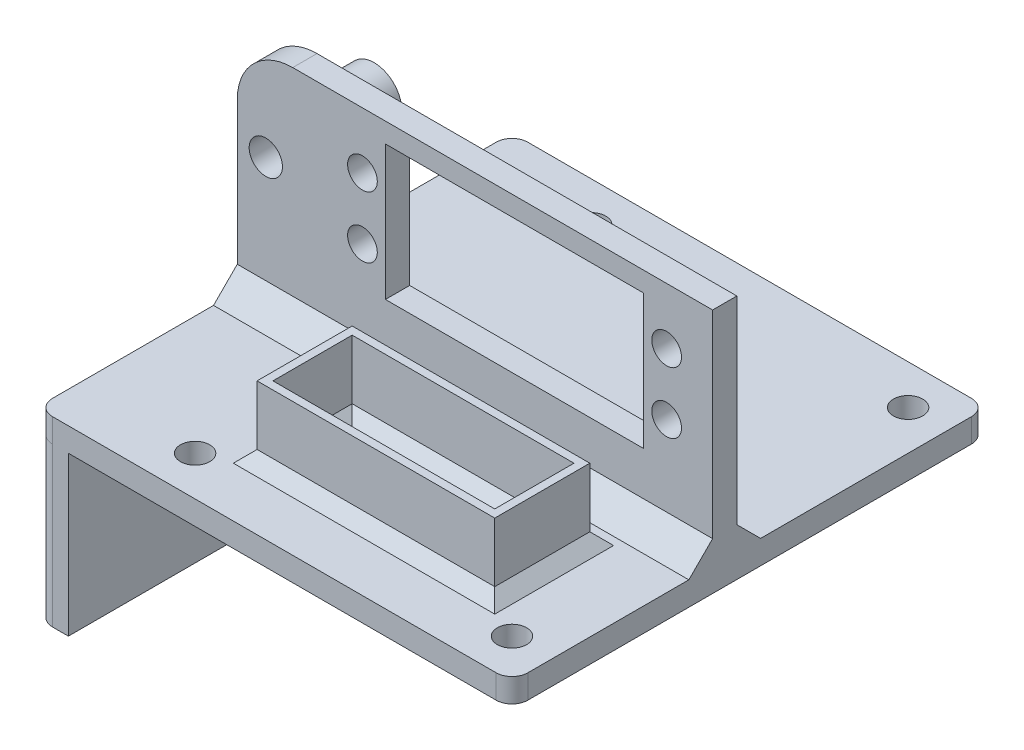
SolidWorks part; units mm, degrees
material "PET"
ref_plane "Front Plane" through (0, 0, 0) normal (0, 0, 1) x (1, 0, 0)
ref_plane "Top Plane" through (0, 0, 0) normal (0, 1, 0) x (1, 0, 0)
ref_plane "Right Plane" through (0, 0, 0) normal (1, 0, 0) x (0, 0, -1)
sketch "Sketch1" plane through (0, 0, 0) normal (0, 0, 1) x (1, 0, 0)
  line L1 (-38.1, -17.78) -> (38.1, -17.78)
  line L2 (-38.1, -17.78) -> (-38.1, 17.78)
  line L3 (-38.1, 17.78) -> (38.1, 17.78)
  line L4 (38.1, -17.78) -> (38.1, 17.78)
  line L5 (-38.1, -17.78) -> (38.1, 17.78) construction
  line L6 (-38.1, 17.78) -> (38.1, -17.78) construction
  point P0 (0, 0)
  dimension "D1" = 76.2
  dimension "D2" = 35.56
extrude "Boss-Extrude1" add sketch "Sketch1" along normal mid plane 3.81
sketch "Sketch2" plane through (0, 0, 1.905) normal (0, 0, 1) x (1, 0, 0)
  line L0 (0, 17.78) -> (0, 0) construction
  line L1 (38.1, 17.78) -> (-38.1, 17.78) construction
  line L2 (6.35, 3.81) -> (30.734, 3.81) construction
  line L5 (-18.034, -1.1149) -> (30.734, -1.1149) construction
  line L6 (-18.034, -1.1149) -> (-18.034, 8.7349) construction
  line L7 (-18.034, 8.7349) -> (30.734, 8.7349) construction
  line L8 (30.734, -1.1149) -> (30.734, 8.7349) construction
  line L9 (-18.034, -1.1149) -> (30.734, 8.7349) construction
  line L10 (-18.034, 8.7349) -> (30.734, -1.1149) construction
  line L11 (6.35, 3.81) -> (6.35, 8.7349) construction
  circle A0 centre (-18.034, 8.7349) radius 2.3813
  circle A1 centre (30.734, 8.7349) radius 2.3812
  circle A2 centre (30.734, -1.1149) radius 2.3812
  circle A3 centre (-18.034, -1.1149) radius 2.3813
  point P9 (6.35, 3.81)
  dimension "D4" = 4.7625
  dimension "D1" = 3.81
  dimension "D2" = 48.768
  dimension "D3" = 9.8499
  dimension "D5" = 6.35
extrude "Cut-Extrude1" cut sketch "Sketch2" against normal blind 6.35
sketch "Sketch3" plane through (0, 0, 1.905) normal (0, 0, 1) x (1, 0, 0)
  line L1 (-18.034, 8.7349) -> (-18.034, -1.1149) construction
  line L2 (-14.351, -6.985) -> (27.051, -6.985)
  line L3 (-14.351, -6.985) -> (-14.351, 14.605)
  line L4 (-14.351, 14.605) -> (27.051, 14.605)
  line L5 (27.051, -6.985) -> (27.051, 14.605)
  line L6 (-14.351, -6.985) -> (27.051, 14.605) construction
  line L7 (-14.351, 14.605) -> (27.051, -6.985) construction
  line L8 (-18.034, 3.81) -> (38.1, 3.81) construction
  line L10 (38.1, -17.78) -> (38.1, 17.78) construction
  point P0 (6.35, 3.81)
  point P6 (6.35, 3.81)
  dimension "D1" = 21.59
  dimension "D2" = 6.35
  dimension "D3" = 41.402
extrude "Cut-Extrude2" cut sketch "Sketch3" against normal up to surface (3.81 mm away) up to face at (-20.4153, -1.1149, -1.905)
sketch "Sketch5" plane through (0, -17.78, 0) normal (0, -1, 0) x (1, 0, 0)
  line L0 (-38.1, 1.905) -> (-38.1, -1.905) construction
  line L1 (-38.1, -26.67) -> (38.1, -26.67)
  line L2 (-38.1, -26.67) -> (-38.1, 49.53)
  line L3 (-38.1, 49.53) -> (38.1, 49.53)
  line L4 (38.1, -26.67) -> (38.1, 49.53)
  line L5 (-38.1, -26.67) -> (38.1, 49.53) construction
  line L6 (-38.1, 49.53) -> (38.1, -26.67) construction
  point P0 (0, 11.43)
  dimension "D1" = 76.2
  dimension "D2" = 76.2
  dimension "D3" = 11.43
extrude "Boss-Extrude2" add sketch "Sketch5" along normal blind 3.81
sketch "Sketch8" plane through (0, 0, -1.905) normal (0, 0, -1) x (-1, 0, 0)
  line L0 (-38.1, 17.78) -> (38.1, 17.78) construction
  line L1 (38.1, 17.78) -> (38.1, -17.78) construction
  circle A0 centre (33.528, 3.175) radius 2.667
  dimension "D1" = 5.334
  dimension "D2" = 14.605
  dimension "D3" = 4.572
extrude "Cut-Extrude5" cut sketch "Sketch8" against normal up to surface (3.81 mm away) up to face at (6.35, 3.81, 1.905)
sketch "Sketch9" plane through (0, 0, -1.905) normal (0, 0, -1) x (-1, 0, 0)
  circle A0 centre (33.528, 3.175) radius 2.667
  circle A1 centre (33.528, 3.175) radius 4.445
  circle A2 centre (33.528, 3.175) radius 2.667 construction
  circle M3 centre (33.528, 3.175) radius 2.667
  dimension "D1" = 8.89
extrude "Boss-Extrude4" add sketch "Sketch9" along normal blind 6.096 contours A1 M3 | A0
sketch "Sketch10" plane through (0, 0, -1.905) normal (0, 0, -1) x (-1, 0, 0)
  line L0 (38.1, -17.78) -> (-38.1, -17.78) construction
  line L1 (30.0355, 0.4254) -> (37.0205, 0.4254)
  line L2 (30.0355, 0.4254) -> (30.0355, -17.78)
  line L3 (30.0355, -17.78) -> (37.0205, -17.78)
  line L4 (37.0205, 0.4254) -> (37.0205, -17.78)
  line L5 (33.528, 5.842) -> (33.528, -21.59) construction
  line L6 (38.1, -21.59) -> (-38.1, -21.59) construction
  circle A0 centre (33.528, 3.175) radius 4.445 construction
  circle A1 centre (33.528, 3.175) radius 2.667 construction
  point P15 (33.528, 0.4254)
  dimension "D1" = 6.985
extrude "Boss-Extrude5" add sketch "Sketch10" along normal up to surface (6.096 mm away) up to face at (-36.195, 3.175, -8.001)
sketch "Sketch11" plane through (0, 0, 1.905) normal (0, 0, 1) x (1, 0, 0)
  circle A0 centre (-33.528, 3.175) radius 2.667
  circle A1 centre (-33.528, 3.175) radius 4.445
  circle A2 centre (-33.528, 3.175) radius 2.667 construction
  dimension "D1" = 8.89
extrude "Boss-Extrude6" add sketch "Sketch11" along normal blind 5.08
sketch "Sketch12" plane through (0, 0, 1.905) normal (0, 0, 1) x (1, 0, 0)
  line L0 (-33.528, 5.842) -> (-33.528, -17.78) construction
  line L1 (38.1, -17.78) -> (-38.1, -17.78) construction
  line L2 (-38.1, -17.78) -> (38.1, -17.78) construction
  line L3 (-37.0205, 0.4254) -> (-30.0355, 0.4254)
  line L4 (-37.0205, 0.4254) -> (-37.0205, -17.78)
  line L5 (-37.0205, -17.78) -> (-30.0355, -17.78)
  line L6 (-30.0355, 0.4254) -> (-30.0355, -17.78)
  circle A0 centre (-33.528, 3.175) radius 2.667 construction
  circle A1 centre (-33.528, 3.175) radius 4.445 construction
  point P6 (-33.528, 3.175)
  point P16 (-33.528, -17.78)
  dimension "D1" = 6.985
extrude "Boss-Extrude7" add sketch "Sketch12" along normal up to surface (5.08 mm away) up to face at (-29.083, 3.175, 6.985)
sketch "Sketch13" plane through (0, -17.78, 0) normal (0, 1, 0) x (1, 0, 0)
  line L0 (0, -49.53) -> (0, 26.67) construction
  line L1 (38.1, -49.53) -> (-38.1, -49.53) construction
  line L2 (-38.1, 26.67) -> (38.1, 26.67) construction
  line L3 (-38.1, 0) -> (38.1, 0) construction
  line L4 (-38.1, -1.905) -> (-38.1, 1.905) construction
  line L5 (38.1, -1.905) -> (38.1, 1.905) construction
  line L8 (-38.1, 1.905) -> (-38.1, 26.67) construction
  line L9 (38.1, 26.67) -> (38.1, 1.905) construction
  line L10 (-38.1, 26.67) -> (-38.1, -49.53) construction
  line L11 (-38.1, -49.53) -> (-38.1, -1.905) construction
  line L12 (-38.1, -11.43) -> (38.1, -11.43) construction
  line L13 (38.1, -1.905) -> (38.1, -49.53) construction
  circle A4 centre (-19.05, 20.32) radius 2.3495
  circle A6 centre (31.75, 20.32) radius 2.3495
  circle A7 centre (31.75, -43.18) radius 2.3495
  circle A8 centre (-19.05, -43.18) radius 2.3495
  dimension "D6" = 4.699
  dimension "D7" = 19.05
  dimension "D8" = 6.35
  dimension "D9" = 6.35
  dimension "D10" = 6.35
extrude "Cut-Extrude6" cut sketch "Sketch13" against normal through all
sketch "Sketch14" plane through (0, 0, 1.905) normal (0, 0, 1) x (1, 0, 0)
  line L0 (-14.351, -6.985) -> (27.051, -6.985) construction
  line L1 (27.051, -6.985) -> (27.051, 14.605) construction
  line L2 (-14.351, 14.605) -> (-14.351, -6.985) construction
  line L3 (27.051, 14.605) -> (-14.351, 14.605) construction
  line L4 (-14.351, -6.985) -> (27.051, -6.985)
  line L5 (27.051, -6.985) -> (27.051, 14.605)
  line L6 (-14.351, 14.605) -> (-14.351, -6.985)
  line L7 (-37.0205, -17.78) -> (-37.0205, 0.4254)
  line L8 (-30.0355, 0.4254) -> (-30.0355, -17.78)
  line L9 (-30.0355, -17.78) -> (38.1, -17.78)
  line L10 (38.1, -17.78) -> (38.1, 17.78)
  line L11 (38.1, 17.78) -> (-38.1, 17.78)
  line L12 (-38.1, 17.78) -> (-38.1, -17.78)
  line L13 (-38.1, -17.78) -> (-37.0205, -17.78)
  line L16 (-30.0355, -17.78) -> (38.1, -17.78)
  line L17 (38.1, -17.78) -> (38.1, 17.78)
  line L18 (38.1, 17.78) -> (-38.1, 17.78)
  line L19 (-38.1, 17.78) -> (-38.1, -17.78)
  line L20 (-38.1, -17.78) -> (-37.0205, -17.78)
  line L21 (27.051, 14.605) -> (-14.351, 14.605)
  line L22 (-37.0205, -17.78) -> (-30.0355, -17.78)
  circle A0 centre (30.734, -1.1149) radius 2.3812 construction
  arc A1 (-30.0355, 0.4254) -> (-37.0205, 0.4254) centre (-33.528, 3.175) ccw
  circle A3 centre (30.734, 8.7349) radius 2.3812 construction
  circle A4 centre (-18.034, -1.1149) radius 2.3813 construction
  circle A5 centre (-18.034, 8.7349) radius 2.3813 construction
  circle A6 centre (30.734, -1.1149) radius 2.3812
  circle A7 centre (30.734, 8.7349) radius 2.3812
  circle A8 centre (-18.034, -1.1149) radius 2.3813
  circle A9 centre (-18.034, 8.7349) radius 2.3813
  circle A10 centre (-33.528, 3.175) radius 2.667 construction
  circle A11 centre (-33.528, 3.175) radius 2.667
  dimension "D1" = 0
extrude "Boss-Extrude8" add sketch "Sketch14" along normal blind 15.466
sketch "Sketch15" plane through (0, 0, -1.905) normal (0, 0, -1) x (-1, 0, 0)
  line L0 (14.351, -6.985) -> (-27.051, -6.985) construction
  line L1 (14.351, 14.605) -> (14.351, -6.985) construction
  line L2 (-27.051, -6.985) -> (-27.051, 14.605) construction
  line L3 (-27.051, 14.605) -> (14.351, 14.605) construction
  line L4 (14.351, -6.985) -> (-27.051, -6.985)
  line L5 (14.351, 14.605) -> (14.351, -6.985)
  line L6 (-27.051, -6.985) -> (-27.051, 14.605)
  line L7 (-38.1, -17.78) -> (30.0355, -17.78)
  line L8 (30.0355, -17.78) -> (30.0355, 0.4254)
  line L9 (37.0205, 0.4254) -> (37.0205, -17.78)
  line L10 (37.0205, -17.78) -> (38.1, -17.78)
  line L11 (38.1, -17.78) -> (38.1, 17.78)
  line L12 (38.1, 17.78) -> (-38.1, 17.78)
  line L13 (-38.1, 17.78) -> (-38.1, -17.78)
  line L14 (-38.1, -17.78) -> (30.0355, -17.78)
  line L15 (30.0355, -17.78) -> (30.0355, 0.4254)
  line L16 (37.0205, 0.4254) -> (37.0205, -17.78)
  line L17 (37.0205, -17.78) -> (38.1, -17.78)
  line L18 (38.1, -17.78) -> (38.1, 17.78)
  line L19 (38.1, 17.78) -> (-38.1, 17.78)
  line L20 (-38.1, 17.78) -> (-38.1, -17.78)
  line L21 (-27.051, 14.605) -> (14.351, 14.605)
  circle A0 centre (18.034, -1.1149) radius 2.3813 construction
  arc A1 (37.0205, 0.4254) -> (30.0355, 0.4254) centre (33.528, 3.175) ccw
  arc A2 (37.0205, 0.4254) -> (30.0355, 0.4254) centre (33.528, 3.175) ccw
  circle A3 centre (18.034, 8.7349) radius 2.3813 construction
  circle A4 centre (-30.734, -1.1149) radius 2.3812 construction
  circle A5 centre (-30.734, 8.7349) radius 2.3812 construction
  circle A6 centre (18.034, -1.1149) radius 2.3813
  circle A7 centre (18.034, 8.7349) radius 2.3813
  circle A8 centre (-30.734, -1.1149) radius 2.3812
  circle A9 centre (-30.734, 8.7349) radius 2.3812
  dimension "D1" = 0
extrude "Cut-Extrude7" cut sketch "Sketch15" against normal blind 15.39
sketch "Sketch16" plane through (0, 0, -8.001) normal (0, 0, -1) x (-1, 0, 0)
  line L3 (30.0355, 0.4254) -> (30.0355, -17.78)
  line L4 (30.0355, -17.78) -> (37.0205, -17.78)
  line L5 (37.0205, -17.78) -> (37.0205, 0.4254)
  line L6 (30.0355, 0.4254) -> (30.0355, -17.78)
  line L7 (30.0355, -17.78) -> (37.0205, -17.78)
  line L8 (37.0205, -17.78) -> (37.0205, 0.4254)
  circle A0 centre (33.528, 3.175) radius 2.667 construction
  arc A1 (37.0205, 0.4254) -> (30.0355, 0.4254) centre (33.528, 3.175) ccw
  arc A2 (37.0205, 0.4254) -> (30.0355, 0.4254) centre (33.528, 3.175) ccw
  circle A3 centre (33.528, 3.175) radius 2.667
  dimension "D1" = 0
extrude "Cut-Extrude8" cut sketch "Sketch16" against normal blind 8.001
fillet "Fillet1" radius 2.54 4 edges at (38.1, -19.685, 49.53) (38.1, -19.685, -26.67) (-38.1, -19.685, -26.67) (-38.1, -19.685, 49.53)
chamfer "Chamfer1" distance 3.81 angle 45 2 edges at (4.0322, -17.78, 13.485) (0, -17.78, 17.371)
fillet "Fillet2" radius 8.89 1 edges at (-38.1, 17.78, 15.428)
sketch "Sketch17" plane through (0, 0, -26.67) normal (0, 0, -1) x (-1, 0, 0)
  line L1 (38.1, -21.59) -> (33.02, -21.59)
  line L2 (38.1, -21.59) -> (38.1, -46.99)
  line L3 (38.1, -46.99) -> (33.02, -46.99)
  line L4 (33.02, -21.59) -> (33.02, -46.99)
  dimension "D1" = 25.4
  dimension "D2" = 5.08
extrude "Boss-Extrude9" add sketch "Sketch17" against normal up to surface (76.2 mm away) up to face at (0, -19.685, 49.53)
sketch "Sketch18" plane through (0, -17.78, 0) normal (0, 1, 0) x (1, 0, 0)
  line L1 (-12.7, -24.356) -> (25.4, -24.356)
  line L2 (-12.7, -24.356) -> (-12.7, -39.596)
  line L3 (-12.7, -39.596) -> (25.4, -39.596)
  line L4 (25.4, -24.356) -> (25.4, -39.596)
  line L6 (38.1, -21.181) -> (38.1, -46.99) construction
  line L7 (-11.43, -25.626) -> (-11.43, -38.326)
  line L8 (-11.43, -38.326) -> (24.13, -38.326)
  line L9 (24.13, -25.626) -> (24.13, -38.326)
  line L10 (-11.43, -25.626) -> (24.13, -25.626)
  line L11 (38.1, -21.181) -> (-38.1, -21.181) construction
  line M6 (38.1, -21.181) -> (-38.1, -21.181)
  dimension "D1" = 38.1
  dimension "D2" = 15.24
  dimension "D3" = 12.7
  dimension "D5" = 3.175
  dimension "D4" = 1.27
extrude "Boss-Extrude10" add sketch "Sketch18" along normal blind 11.43 contours L4 L2 L3 L7 L10 L9 L8 M6
chamfer "Chamfer2" distance 1.905 angle 45 8 edges at (6.35, -17.78, 24.356) (-12.7, -17.78, 31.976) (25.4, -17.78, 31.976) (6.35, -17.78, 39.596) (6.35, -17.78, 38.326) (-11.43, -17.78, 31.976) (6.35, -17.78, 25.626) (24.13, -17.78, 31.976)
fillet "Fillet3" radius 2.54 2 edges at (-38.1, -34.29, 49.53) (-38.1, -34.29, -26.67)
sketch "Sketch19" plane through (-38.1, 0, 0) normal (-1, 0, 0) x (0, 0, 1)
  line L0 (11.43, -46.99) -> (11.43, -17.78) construction
  line L1 (46.99, -46.99) -> (-24.13, -46.99) construction
  line L2 (0, -17.78) -> (13.485, -17.78) construction
  line L3 (11.43, -32.385) -> (-24.13, -32.385) construction
  line L4 (-24.13, -21.59) -> (-24.13, -46.99) construction
  circle A0 centre (-7.62, -32.385) radius 2.3495
  circle A2 centre (30.48, -32.385) radius 2.3495
  dimension "D1" = 4.699
  dimension "D2" = 19.05
extrude "Cut-Extrude9" cut sketch "Sketch19" against normal blind 8.89
sketch "Sketch20" plane through (0, 0, 0) normal (0, 0, -1) x (-1, 0, 0)
  line L0 (37.0205, 0.4254) -> (37.0205, -17.78) construction
  line L1 (30.0355, -17.78) -> (37.0205, -17.78)
  line L2 (30.0355, -17.78) -> (30.0355, -1.27)
  line L3 (30.0355, -1.27) -> (37.0205, -1.27)
  line L4 (37.0205, -17.78) -> (37.0205, -1.27)
  dimension "D1" = 16.51
extrude "Cut-Extrude10" cut sketch "Sketch20" against normal blind 1.27
fillet "Fillet4" radius 2.54 1 edges at (-33.528, -1.27, 1.27)
